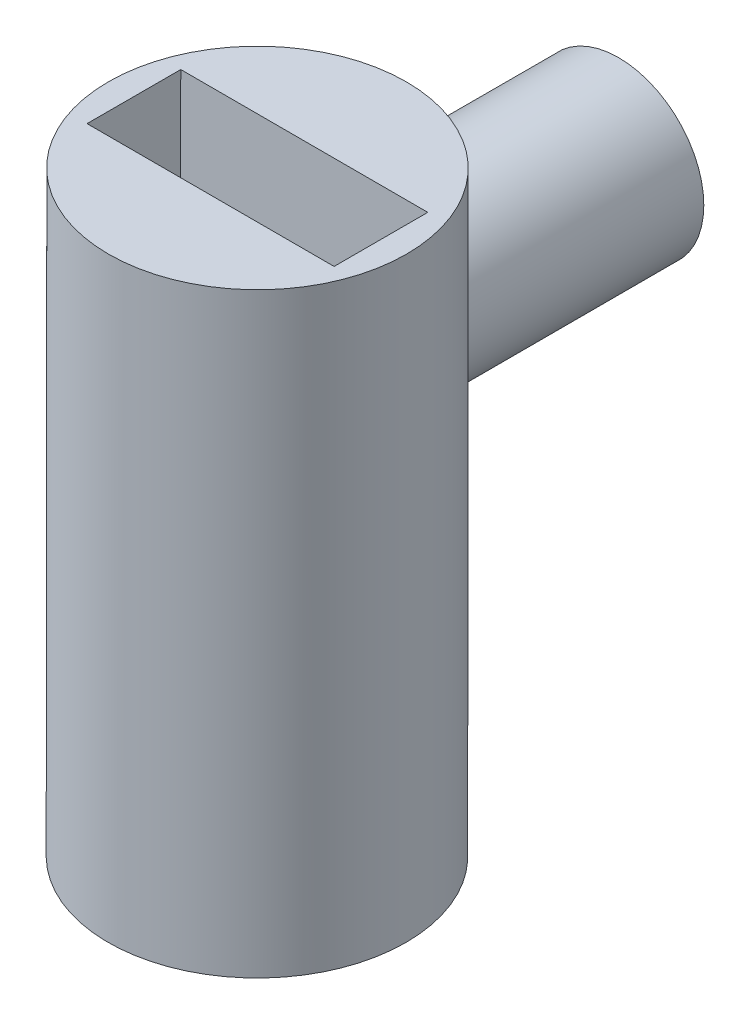
SolidWorks part; units mm, degrees
ref_plane "Front" through (0, 0, 0) normal (0, 0, 1) x (1, 0, 0)
ref_plane "Top" through (0, 0, 0) normal (0, 1, 0) x (1, 0, 0)
ref_plane "Right" through (0, 0, 0) normal (1, 0, 0) x (0, 0, -1)
sketch "Sketch3" plane through (0, 96.8586, 4.3621) normal (-0.0007, -1, 0) x (1, -0.0007, 0)
  circle A0 centre (0, 0) radius 6.75
  circle A1 centre (0, 0) radius 8.75
  dimension "D1" = 13.5
  dimension "D2" = 2
extrude "Boss-Extrude2" add sketch "Sketch3" along normal blind 20 separate body
sketch "Sketch1" plane through (0, 0, 0) normal (0, 0, 1) x (1, 0, 0)
  line L0 (-2.24, 103.1286) -> (2.24, 103.1286)
  arc A0 (-2.24, 103.1286) -> (2.24, 103.1286) centre (0, 101.8586) ccw
  circle A2 centre (0, 101.8586) radius 1.5 construction
  arc A3 (2.24, 103.1286) -> (-2.24, 103.1286) centre (0, 101.8586) ccw construction
  circle A4 centre (0, 101.8586) radius 5
  dimension "D1" = 5.15
  dimension "D3" = 10
  dimension "D2" = 4.48
extrude "Boss-Extrude1" add sketch "Sketch1" against normal offset from surface (16.85 mm away) 0.15
sketch "Sketch4" plane through (0.0693, 96.8585, 0) normal (0.0007, 1, 0) x (1, -0.0007, 0)
  line L1 (-7.3193, -7.1121) -> (7.1807, -7.1121)
  line L2 (-7.3193, -7.1121) -> (-7.3193, -1.6121)
  line L3 (-7.3193, -1.6121) -> (7.1807, -1.6121)
  line L4 (7.1807, -7.1121) -> (7.1807, -1.6121)
  line L5 (-7.3193, -7.1121) -> (7.1807, -1.6121) construction
  line L6 (-7.3193, -1.6121) -> (7.1807, -7.1121) construction
  line L14 (6.9307, -1.8621) -> (-7.0693, -1.8621) construction
  line L15 (-7.0693, -1.8621) -> (-7.0693, -6.8621) construction
  line L16 (-7.0693, -6.8621) -> (6.9307, -6.8621) construction
  line L17 (6.9307, -6.8621) -> (6.9307, -1.8621) construction
  circle A0 centre (-0.0693, -4.3621) radius 8.75
  circle A1 centre (-0.0693, -4.3621) radius 8.75 construction
  point P0 (-0.0693, -4.3621)
  dimension "D1" = 0.25
  dimension "D2" = 0.25
  dimension "D3" = 0.25
  dimension "D4" = 0.25
extrude "Boss-Extrude3" add sketch "Sketch4" along normal blind 15
sketch "Sketch2" plane through (0, 0, -16.85) normal (0, 0, -1) x (-1, 0, 0)
  circle A0 centre (0, 101.8586) radius 2.575
  dimension "D1" = 5.15
extrude "Cut-Extrude1" cut sketch "Sketch2" against normal blind 5
sketch "Sketch5" plane through (0, 0, -16.85) normal (0, 0, -1) x (-1, 0, 0)
  line L0 (-2.24, 103.1286) -> (2.24, 103.1286) construction
  line L1 (-2.24, 103.1286) -> (2.24, 103.1286)
  circle A0 centre (0, 101.8586) radius 2.575 construction
  arc A1 (-2.24, 103.1286) -> (2.24, 103.1286) centre (0, 101.8586) ccw
  arc A2 (2.24, 103.1286) -> (-2.24, 103.1286) centre (0, 101.8586) ccw construction
extrude "Cut-Extrude2" cut sketch "Sketch5" against normal blind 20
